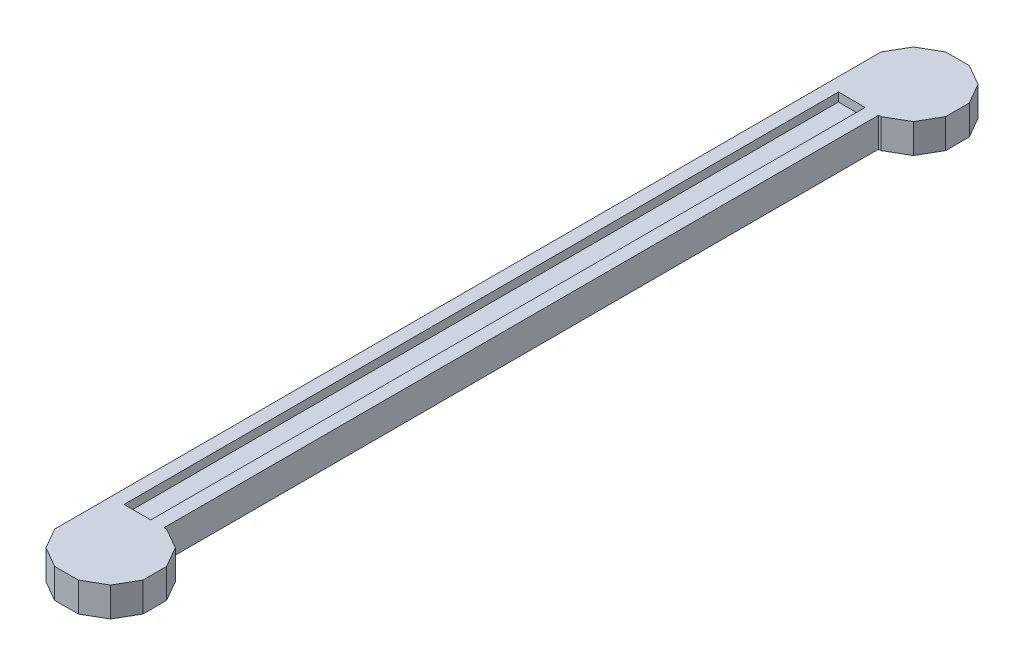
SolidWorks part; units mm, degrees
ref_plane "Front Plane" through (0, 0, 0) normal (0, 0, 1) x (1, 0, 0)
ref_plane "Top Plane" through (0, 0, 0) normal (0, 1, 0) x (1, 0, 0)
ref_plane "Right Plane" through (0, 0, 0) normal (1, 0, 0) x (0, 0, -1)
ref_plane "Plane1" through (0, 11, 0) normal (0, 1, 0) x (1, 0, 0)
sketch "Sketch1" plane through (0, 11, 0) normal (0, 1, 0) x (1, 0, 0)
  line L0 (24.1577, 24.1577) -> (8.8423, 33)
  line L1 (8.8423, 33) -> (-8.8423, 33)
  line L2 (-8.8423, 33) -> (-24.1577, 24.1577)
  line L3 (-24.1577, 24.1577) -> (-33, 8.8423)
  line L4 (-33, 8.8423) -> (-33, -608.8423)
  line L5 (-33, -608.8423) -> (-24.1577, -624.1577)
  line L6 (-24.1577, -624.1577) -> (-8.8423, -633)
  line L7 (-8.8423, -633) -> (8.8423, -633)
  line L8 (8.8423, -633) -> (24.1577, -624.1577)
  line L9 (24.1577, -624.1577) -> (33, -608.8423)
  line L10 (33, -608.8423) -> (33, 8.8423)
  line L11 (33, 8.8423) -> (24.1577, 24.1577)
extrude "Boss-Extrude1" add sketch "Sketch1" against normal blind 22
sketch "Sketch2" plane through (0, -11, 0) normal (0, -1, 0) x (1, 0, 0)
  line L0 (33, 8.8423) -> (33, 591.1577)
  line L1 (33, 591.1577) -> (24.1577, 575.8423)
  line L2 (24.1577, 575.8423) -> (8.8423, 567)
  line L3 (8.8423, 567) -> (7, 567)
  line L4 (7, 567) -> (7, 33)
  line L5 (7, 33) -> (8.8423, 33)
  line L6 (8.8423, 33) -> (24.1577, 24.1577)
  line L7 (24.1577, 24.1577) -> (33, 8.8423)
extrude "Cut-Extrude1" cut sketch "Sketch2" against normal through all
sketch "Sketch3" plane through (0, -11, 0) normal (0, -1, 0) x (1, 0, 0)
  line L0 (-3, 567) -> (-23, 567)
  line L1 (-23, 567) -> (-23, 33)
  line L2 (-23, 33) -> (-3, 33)
  line L3 (-3, 33) -> (-3, 567)
extrude "Cut-Extrude2" cut sketch "Sketch3" against normal blind 6.5
sketch "Sketch4" plane through (0, 11, 0) normal (0, 1, 0) x (-1, 0, 0)
  line L0 (3, 33) -> (23, 33)
  line L1 (23, 33) -> (23, 567)
  line L2 (23, 567) -> (3, 567)
  line L3 (3, 567) -> (3, 33)
extrude "Cut-Extrude3" cut sketch "Sketch4" against normal blind 6.5
sketch "Sketch5" plane through (0, 11, 0) normal (0, 1, 0) x (1, 0, 0)
  line L0 (0, 0) -> (0.2617, -649.2177) construction
  line L1 (-8.8423, -633) -> (8.8423, -633) construction
  line L2 (24.1577, -575.8423) -> (8.8423, -567) construction
  circle A0 centre (0.2419, -600.0648) radius 32.9352
  circle A1 centre (0, 0) radius 33
ref_axis "Axis1" through (0.2419, 11, 600.0648) along (0, -1, 0)
ref_axis "Axis2" through (0, -34.131, 0) along (0, 1, 0)
